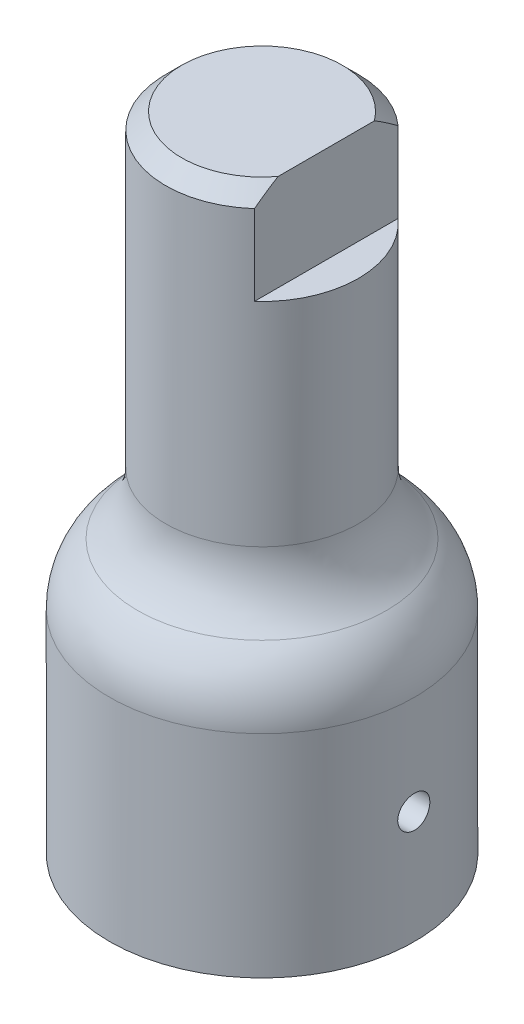
SolidWorks part; units mm, degrees
ref_plane "Front Plane" through (0, 0, 0) normal (0, 0, 1) x (1, 0, 0)
ref_plane "Top Plane" through (0, 0, 0) normal (0, 1, 0) x (1, 0, 0)
ref_plane "Right Plane" through (0, 0, 0) normal (1, 0, 0) x (0, 0, -1)
sketch "Sketch1" plane through (0, 0, 0) normal (0, 1, 0) x (1, 0, 0)
  line L0 (4, 4.4721) -> (4, -4.4721)
  circle A0 centre (0, 0) radius 9.5
  circle A1 centre (0, 0) radius 6
  point P6 (0, 0)
  point P7 (0, 0)
  dimension "D1" = 19
  dimension "D2" = 12
  dimension "D3" = 4
extrude "Boss-Extrude1" add sketch "Sketch1" along normal blind 16 contours A0 A1 region at (-9.2313, 0, 0)
extrude "Boss-Extrude2" add sketch "Sketch1<3>" along normal blind 26 from offset 14 separate body contours L0 A1 region at (-0.5921, 0, 0)
sketch "Sketch1<3>" plane through (0, 0, 0) normal (0, 1, 0) x (1, 0, 0) same geometry as "Sketch1"
extrude "Boss-Extrude5" add sketch "Sketch1<5>" along normal blind 20 from offset 14 contours L0 A1 region at (4.8127, 0, 0)
sketch "Sketch1<5>" plane through (0, 0, 0) normal (0, 1, 0) x (1, 0, 0) same geometry as "Sketch1"
sketch "Sketch2" plane through (0, 0, 0) normal (1, 0, 0) x (0, 0, -1)
  line L0 (-6, 0) -> (6, 0) construction
  circle A0 centre (0, 7) radius 1
  point P4 (0, 0)
  dimension "D1" = 2
  dimension "D2" = 7
extrude "Cut-Extrude1" cut sketch "Sketch2" along normal up to next
chamfer "Chamfer1" distance 1 angle 45 1 edges at (-6, 40, 0)
fillet "Fillet2" radius 5 1 edges at (0, 16, 6)
fillet "Fillet3" radius 5 1 edges at (0, 16, 9.5)
